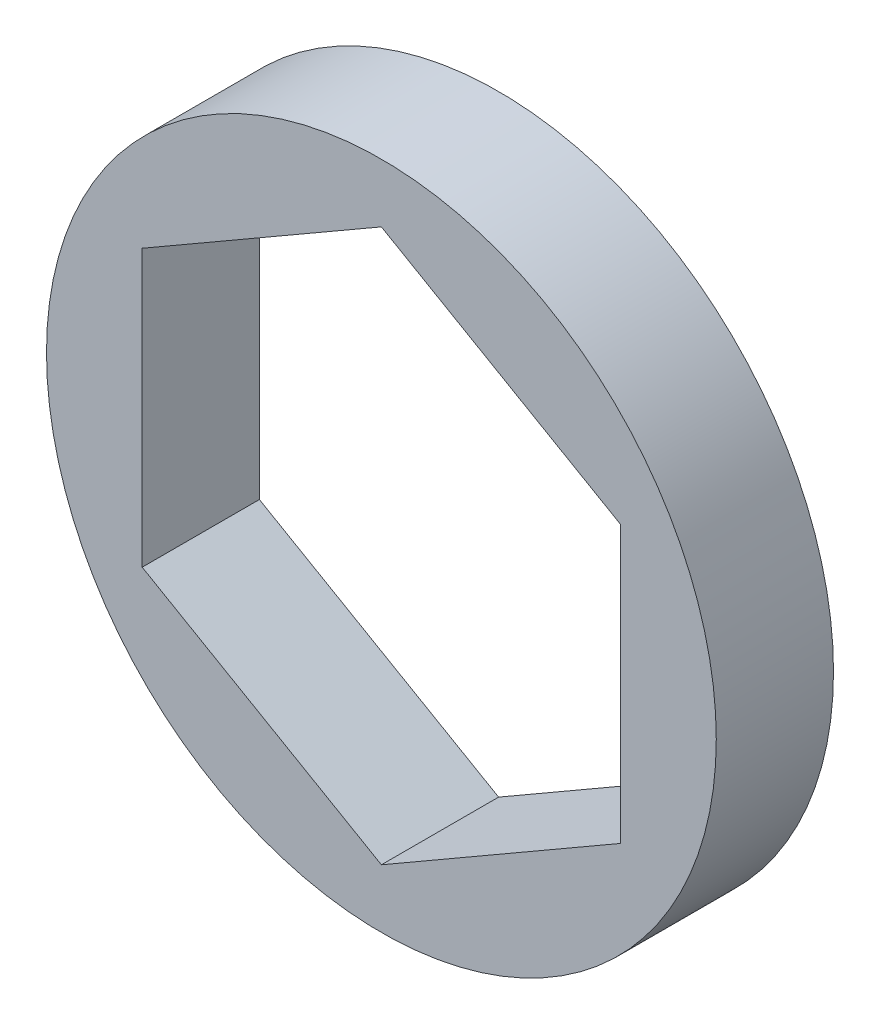
SolidWorks part; units mm, degrees
material "PET"
ref_plane "Front Plane" through (0, 0, 0) normal (0, 0, 1) x (1, 0, 0)
ref_plane "Top Plane" through (0, 0, 0) normal (0, 1, 0) x (1, 0, 0)
ref_plane "Right Plane" through (0, 0, 0) normal (1, 0, 0) x (0, 0, -1)
sketch "Sketch1" plane through (0, 0, 0) normal (0, 0, 1) x (1, 0, 0)
  line L1 (0, 7.3323) -> (-6.35, 3.6662)
  line L2 (-6.35, 3.6662) -> (-6.35, -3.6662)
  line L3 (-6.35, -3.6662) -> (0, -7.3323)
  line L4 (0, -7.3323) -> (6.35, -3.6662)
  line L5 (6.35, -3.6662) -> (6.35, 3.6662)
  line L6 (6.35, 3.6662) -> (0, 7.3323)
  circle A0 centre (0, 0) radius 8.89
  circle A1 centre (0, 0) radius 6.35 construction
  dimension "D1" = 17.78
  dimension "D2" = 12.7
extrude "Boss-Extrude1" add sketch "Sketch1" along normal mid plane 3.1115
